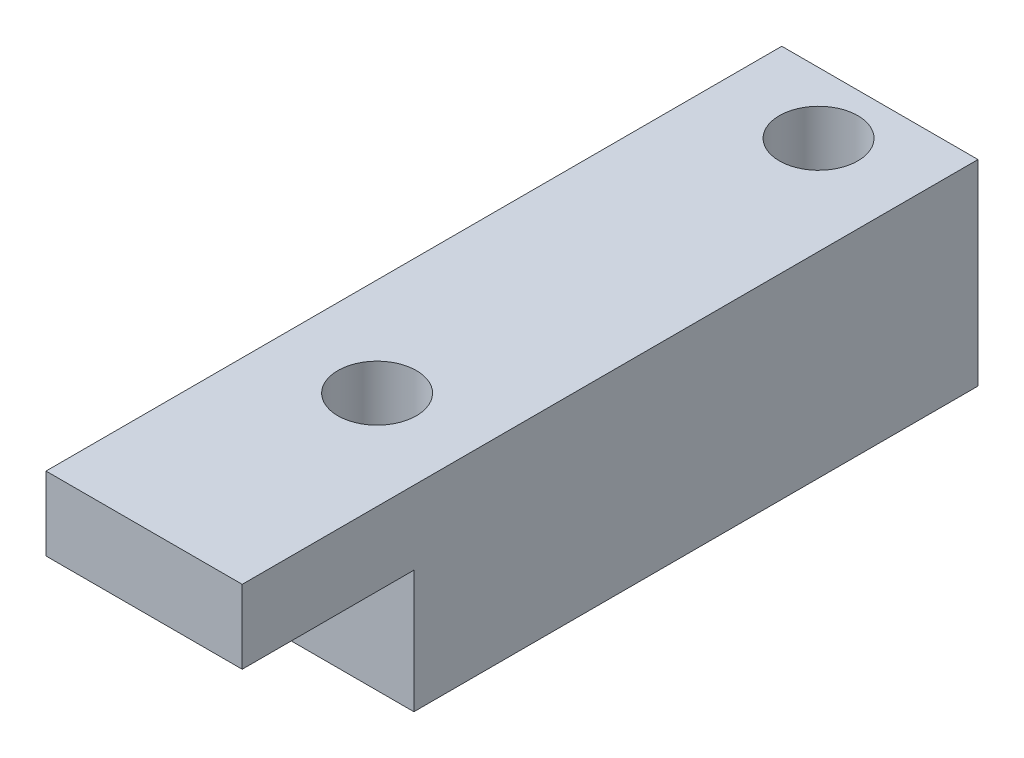
SolidWorks part; units mm, degrees
ref_plane "Front Plane" through (0, 0, 0) normal (0, 0, 1) x (1, 0, 0)
ref_plane "Top Plane" through (0, 0, 0) normal (0, 1, 0) x (1, 0, 0)
ref_plane "Right Plane" through (0, 0, 0) normal (1, 0, 0) x (0, 0, -1)
sketch "Sketch1" plane through (0, 0, 0) normal (0, 1, 0) x (1, 0, 0)
  line L0 (0, 11.5) -> (0, -11.5) construction
  line L1 (-4, -11.5) -> (4, -11.5)
  line L2 (-4, -11.5) -> (-4, 11.5)
  line L3 (-4, 11.5) -> (4, 11.5)
  line L4 (4, -11.5) -> (4, 11.5)
  line L5 (-4, -11.5) -> (4, 11.5) construction
  line L6 (-4, 11.5) -> (4, -11.5) construction
  line L7 (0, 9) -> (4, 0) construction
  line L8 (4, 0) -> (0, -9) construction
  circle A0 centre (0, 9) radius 1.6
  circle A1 centre (0, -9) radius 1.6
  point P0 (0, 0)
  dimension "D1" = 3.2
  dimension "D2" = 18
  dimension "D3" = 23
  dimension "D4" = 8
extrude "Boss-Extrude1" add sketch "Sketch1" along normal blind 5
sketch "Sketch2" plane through (0, 5, 0) normal (0, 1, 0) x (1, 0, 0)
  line L1 (-4, -11.5) -> (4, -11.5) construction
  line L2 (-4, -11.5) -> (-4, -18.5)
  line L3 (-4, -18.5) -> (4, -18.5)
  line L4 (4, -11.5) -> (4, 11.5)
  line L5 (4, 11.5) -> (-4, 11.5)
  line L6 (-4, 11.5) -> (-4, -11.5)
  line L7 (-4, -11.5) -> (4, -11.5)
  line L8 (4, -11.5) -> (4, 11.5)
  line L9 (4, 11.5) -> (-4, 11.5)
  line L10 (-4, 11.5) -> (-4, -11.5)
  line L11 (-4, -11.5) -> (4, -11.5) construction
  line L12 (4, -11.5) -> (4, -18.5)
  circle A0 centre (0, 9) radius 1.6 construction
  circle A1 centre (0, 9) radius 1.6
  circle A2 centre (0, -9) radius 1.6 construction
  circle A3 centre (0, -9) radius 1.6
  dimension "D2" = 7
  dimension "D1" = 0
extrude "Boss-Extrude2" add sketch "Sketch2" along normal blind 3
